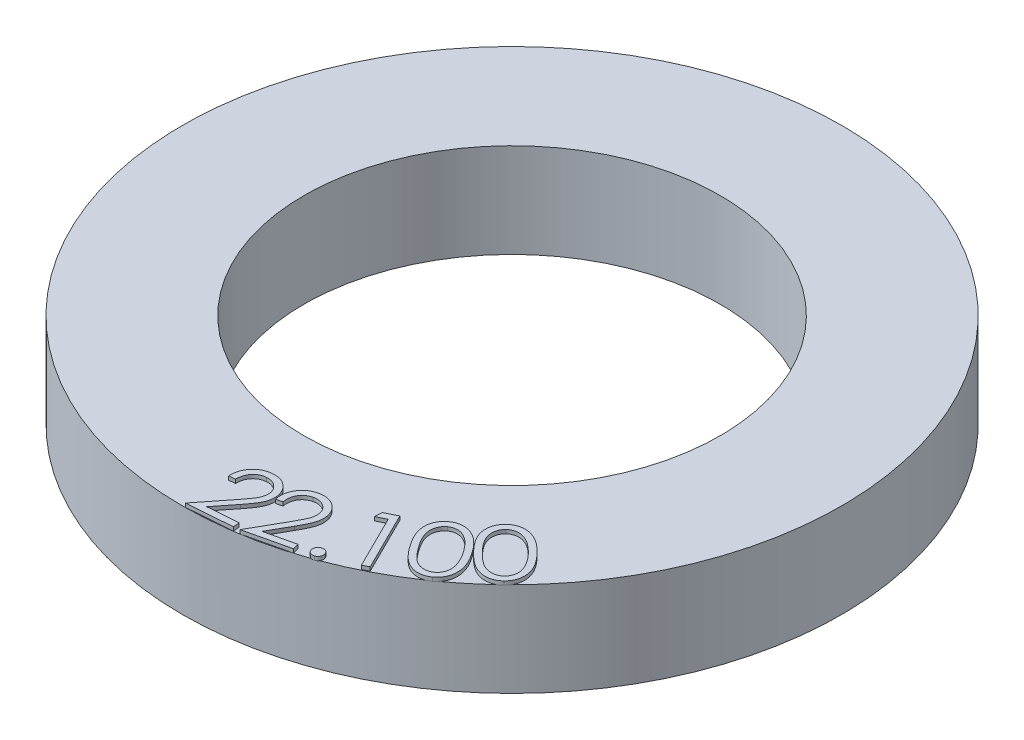
SolidWorks part; units mm, degrees
ref_plane "Front Plane" through (0, 0, 0) normal (0, 0, 1) x (1, 0, 0)
ref_plane "Top Plane" through (0, 0, 0) normal (0, 1, 0) x (1, 0, 0)
ref_plane "Right Plane" through (0, 0, 0) normal (1, 0, 0) x (0, 0, -1)
ref_axis "X" through (-88.99, 0, 0) along (1, 0, 0)
ref_axis "Y" through (0, 55, 0) along (0, -1, 0)
ref_axis "Z" through (0, 0, -88.99) along (0, 0, 1)
sketch "Sketch1" plane through (0, 0, 0) normal (0, 1, 0) x (1, 0, 0)
  circle A0 centre (0, 0) radius 17.5
  circle A1 centre (0, 0) radius 11.05
  dimension "D1" = 35
  dimension "D2" = 22.1
extrude "Boss-Extrude1" add sketch "Sketch1" along normal blind 5
sketch "Sketch5" plane through (0, 5, 0) normal (0, 1, 0) x (1, 0, 0)
  text T0 "22.100\r\n"
extrude "Boss-Extrude5" add sketch "Sketch5" along normal blind 0.2
